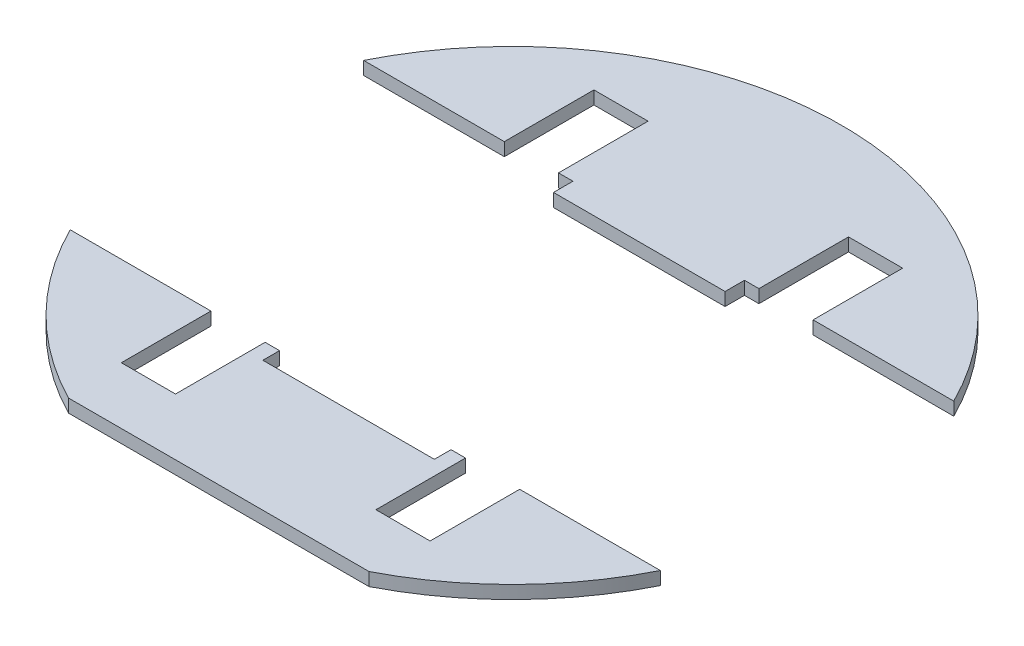
SolidWorks part; units mm, degrees
ref_plane "Front Plane" through (0, 0, 0) normal (0, 0, 1) x (1, 0, 0)
ref_plane "Top Plane" through (0, 0, 0) normal (0, 1, 0) x (1, 0, 0)
ref_plane "Right Plane" through (0, 0, 0) normal (1, 0, 0) x (0, 0, -1)
sketch "Sketch1" plane through (0, 0, 0) normal (0, 1, 0) x (1, 0, 0)
  line L0 (-33.2911, -64.9669) -> (33.2911, -64.9669)
  line L1 (0, -83.8021) -> (0, 0) construction
  line L2 (0, -83.8021) -> (33.2911, -64.9669) construction
  arc A0 (33.2911, -64.9669) -> (-33.2911, -64.9669) centre (0, 0) ccw
  circle A1 centre (0, -83.8021) radius 38.25 construction
  dimension "D1" = 146
  dimension "D2" = 76.5
  dimension "D3" = 60.5
extrude "Boss-Extrude1" add sketch "Sketch1" along normal blind 2.9
sketch "Sketch2" plane through (0, 2.9, 0) normal (0, 1, 0) x (1, 0, 0)
  line L0 (18, -36.2) -> (-18, -36.2) construction
  line L1 (-34.2, -52.3449) -> (-22.2, -52.3449)
  line L2 (-34.2, -52.3449) -> (-34.2, 52.3449)
  line L3 (-34.2, 52.3449) -> (-22.2, 52.3449)
  line L4 (-22.2, -52.3449) -> (-22.2, -32.5)
  line L5 (-19, -32.5) -> (-22.2, -32.5) construction
  line L6 (-22.2, -52.3449) -> (-22.2, -32.5)
  line L7 (-19, -32.5) -> (-22.2, -32.5)
  line L8 (19, 28.2) -> (-19, 28.2) construction
  line L9 (18, -36.2) -> (-18, -36.2)
  line L10 (-19, 32.5) -> (-22.2, 32.5) construction
  line L11 (-19, 32.5) -> (-22.2, 32.5)
  line L12 (19, 28.2) -> (-19, 28.2)
  line L13 (-19, -32.5) -> (-19, -36.2)
  line L14 (-19, -36.2) -> (-18, -36.2)
  line L15 (-19, 32.5) -> (-19, 28.2)
  line L16 (-22.2, 32.5) -> (-22.2, 52.3449)
  line L17 (0, 0) -> (0, -64.9669) construction
  line L18 (-33.2911, -64.9669) -> (33.2911, -64.9669) construction
  line L19 (22.2, 32.5) -> (22.2, 52.3449)
  line L20 (19, 32.5) -> (19, 28.2)
  line L21 (19, -36.2) -> (18, -36.2)
  line L22 (19, -32.5) -> (19, -36.2)
  line L23 (19, 32.5) -> (22.2, 32.5)
  line L24 (19, -32.5) -> (22.2, -32.5)
  line L25 (22.2, -52.3449) -> (22.2, -32.5)
  line L26 (22.2, -52.3449) -> (22.2, -32.5)
  line L27 (34.2, 52.3449) -> (22.2, 52.3449)
  line L28 (34.2, -52.3449) -> (34.2, 52.3449)
  line L29 (34.2, -52.3449) -> (22.2, -52.3449)
extrude "Cut-Extrude1" cut sketch "Sketch2" against normal through all contours L29 L28 L27 L19 L23 L20 L12 L15 L11 L16 L3 L2 L1 L4 L7 L13 L14 L9 L21 L22 L24 L25 region at (0, 2.9, 1.8209)
sketch "Sketch3" plane through (0, 2.9, 0) normal (0, 1, 0) x (1, 0, 0)
  line L0 (-34.2, 32.5) -> (-34.2, -32.5)
  line L1 (-73, -32.5) -> (-34.2, -32.5)
  line L2 (-73, -32.5) -> (-73, 32.5)
  line L3 (-73, 32.5) -> (-34.2, 32.5)
  line L4 (73, -32.5) -> (73, 32.5)
  line L5 (-73, -32.5) -> (73, 32.5) construction
  line L6 (-73, 32.5) -> (73, -32.5) construction
  line L7 (-34.2, -52.3449) -> (-34.2, 52.3449) construction
  line L8 (34.2, 32.5) -> (34.2, -32.5)
  line L9 (34.2, -52.3449) -> (34.2, 52.3449) construction
  line L10 (34.2, 32.5) -> (73, 32.5)
  line L11 (34.2, -32.5) -> (73, -32.5)
  arc A0 (33.2911, -64.9669) -> (-33.2911, -64.9669) centre (0, 0) ccw construction
  point P0 (0, 0)
  dimension "D1" = 65
extrude "Cut-Extrude2" cut sketch "Sketch3" against normal through all
equation "\"smallPulleyTeeth\"= 15"
equation "\"largePulleyTeeth\"= 30"
equation "\"eighthThick\"= 2.9mm"
equation "\"sixteenthThick\" = 1.7mm"
equation "\"quarterThick\"=6.0mm"
equation "\"OD\" = 146mm"
equation "\"puckAngle\" = 60.5deg"
equation "\"puckDiam\" = 76.5mm"
equation "\"axlePress\" = 5.9mm"
equation "\"press\" = 0.2mm"
equation "\"wheelClear\" = 0.3mm"
equation "\"10-32clear\" = 4.8mm"
equation "\"6-32clear\" = 3.3mm"
equation "\"8-32clear\" = 4.0mm"
equation "\"4-40clear\" = 3.0mm"
equation "\"wheelHeight\" = 22mm"
equation "\"wheelWell\" = 65mm"
equation "\"D1@Sketch1\"=\"OD\""
equation "\"D1@Boss-Extrude1\"=\"eighthThick\""
equation "\"D2@Sketch1\"=\"puckDiam\""
equation "\"D3@Sketch1\"=\"puckAngle\""
equation "\"D1@Sketch3\"=\"wheelWell\""
